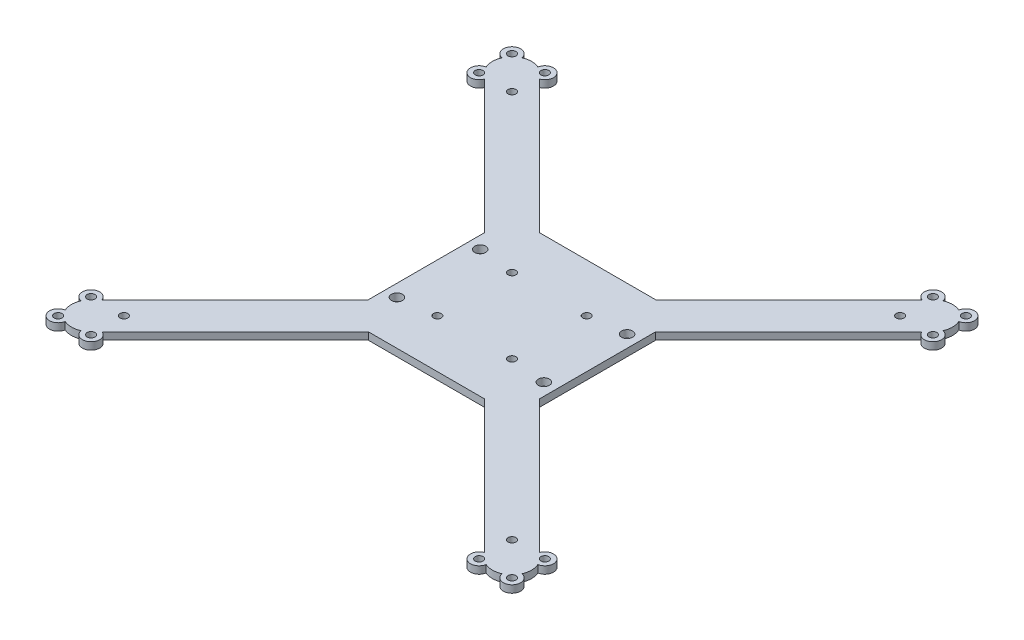
SolidWorks part; units mm, degrees
ref_plane "Front Plane" through (0, 0, 0) normal (0, 0, 1) x (1, 0, 0)
ref_plane "Top Plane" through (0, 0, 0) normal (0, 1, 0) x (1, 0, 0)
ref_plane "Right Plane" through (0, 0, 0) normal (1, 0, 0) x (0, 0, -1)
sketch "Sketch1" plane through (0, 0, 0) normal (0, 1, 0) x (1, 0, 0)
  line L1 (-23.6863, -35) -> (23.6863, -35)
  line L2 (-35, -23.6863) -> (-35, 23.6863)
  line L3 (-23.6863, 35) -> (23.6863, 35)
  line L4 (35, -23.6863) -> (35, 23.6863)
  line L5 (-35, -35) -> (42.6186, 42.6186) construction
  line L6 (-35, 35) -> (35, -35) construction
  line L7 (35, 23.6863) -> (89.3815, 78.0678)
  line L8 (23.6863, 35) -> (78.0678, 89.3815)
  line L9 (0, 0) -> (54.3815, 54.3815) construction
  line L10 (79.2432, 92.6782) -> (92.6782, 79.2432) construction
  line L11 (30, 17) -> (30, 0) construction
  line L12 (0, 0) -> (0, 23.6863) construction
  line L13 (35, -23.6863) -> (89.3815, -78.0678)
  line L14 (23.6863, -35) -> (78.0678, -89.3815)
  line L15 (-23.6863, -35) -> (-78.0678, -89.3815)
  line L16 (-35, -23.6863) -> (-89.3815, -78.0678)
  line L17 (-35, 23.6863) -> (-89.3815, 78.0678)
  line L18 (-23.6863, 35) -> (-78.0678, 89.3815)
  circle A0 centre (-15.25, 15.25) radius 1.6
  circle A1 centre (15.25, 15.25) radius 1.6
  circle A2 centre (15.25, -15.25) radius 1.6
  circle A3 centre (-15.25, -15.25) radius 1.6
  arc A5 (93.2633, 89.2274) -> (89.2274, 93.2633) centre (92.6782, 92.6782) ccw
  arc A9 (93.8536, 82.5399) -> (93.2633, 82.6939) centre (92.6782, 79.2432) ccw
  arc A10 (89.2274, 93.2633) -> (82.6939, 93.2633) centre (85.9607, 85.9607) ccw
  circle A11 centre (92.6782, 92.6782) radius 1.6
  circle A12 centre (92.6782, 79.2432) radius 1.6
  circle A13 centre (79.2432, 79.2432) radius 1.6
  circle A14 centre (79.2432, 92.6782) radius 1.6
  arc A15 (93.2633, 82.6939) -> (93.2633, 89.2274) centre (85.9607, 85.9607) ccw
  arc A16 (82.6939, 93.2633) -> (82.5399, 93.8536) centre (79.2432, 92.6782) ccw
  arc A17 (78.6581, 82.6939) -> (76.7683, 76.7683) centre (79.2432, 79.2432) ccw [skipped]
  circle A18 centre (30, 17) radius 2.25
  circle A19 centre (30, -17) radius 2.25
  circle A20 centre (-30, -17) radius 2.25
  circle A21 centre (-30, 17) radius 2.25
  arc A22 (78.0678, 89.3815) -> (82.5399, 93.8536) centre (79.2432, 92.6782) cw
  arc A23 (93.2633, -89.2274) -> (93.2633, -82.6939) centre (85.9607, -85.9607) ccw
  circle A24 centre (92.6782, 92.6782) radius 1.6
  circle A25 centre (79.2432, 79.2432) radius 1.6
  arc A26 (82.6939, -93.2633) -> (89.2274, -93.2633) centre (85.9607, -85.9607) ccw
  arc A27 (93.8536, 82.5399) -> (89.3815, 78.0678) centre (92.6782, 79.2432) cw
  arc A28 (78.0678, -89.3815) -> (82.6939, -93.2633) centre (79.2432, -92.6782) ccw
  circle A29 centre (79.2432, -92.6782) radius 1.6
  circle A30 centre (79.2432, -79.2432) radius 1.6
  circle A31 centre (92.6782, -79.2432) radius 1.6
  arc A32 (93.2633, -82.6939) -> (89.3815, -78.0678) centre (92.6782, -79.2432) ccw
  arc A33 (89.2274, -93.2633) -> (93.2633, -89.2274) centre (92.6782, -92.6782) ccw
  circle A34 centre (92.6782, -92.6782) radius 1.6
  arc A35 (-89.2274, -93.2633) -> (-82.6939, -93.2633) centre (-85.9607, -85.9607) ccw
  arc A36 (-93.2633, -82.6939) -> (-93.2633, -89.2274) centre (-85.9607, -85.9607) ccw
  arc A37 (-89.3815, -78.0678) -> (-93.2633, -82.6939) centre (-92.6782, -79.2432) ccw
  circle A38 centre (-92.6782, -79.2432) radius 1.6
  circle A39 centre (-79.2432, -79.2432) radius 1.6
  circle A40 centre (-79.2432, -92.6782) radius 1.6
  arc A41 (-82.6939, -93.2633) -> (-78.0678, -89.3815) centre (-79.2432, -92.6782) ccw
  arc A42 (-93.2633, -89.2274) -> (-89.2274, -93.2633) centre (-92.6782, -92.6782) ccw
  circle A43 centre (-92.6782, -92.6782) radius 1.6
  arc A44 (-93.2633, 89.2274) -> (-93.2633, 82.6939) centre (-85.9607, 85.9607) ccw
  arc A45 (-82.6939, 93.2633) -> (-89.2274, 93.2633) centre (-85.9607, 85.9607) ccw
  arc A46 (-78.0678, 89.3815) -> (-82.6939, 93.2633) centre (-79.2432, 92.6782) ccw
  circle A47 centre (-79.2432, 92.6782) radius 1.6
  circle A48 centre (-79.2432, 79.2432) radius 1.6
  circle A49 centre (-92.6782, 79.2432) radius 1.6
  arc A50 (-93.2633, 82.6939) -> (-89.3815, 78.0678) centre (-92.6782, 79.2432) ccw
  arc A51 (-89.2274, 93.2633) -> (-93.2633, 89.2274) centre (-92.6782, 92.6782) ccw
  circle A52 centre (-92.6782, 92.6782) radius 1.6
  point P0 (0, 0)
  point P17 (0, 0)
  point P33 (85.9607, 85.9607)
  point P42 (85.9607, 85.9607)
  point P45 (85.9607, 85.9607)
  point P47 (30, 0)
  point P51 (0, 0)
  point P53 (0, 0)
  point P54 (0, 0)
  point P118 (0, 0)
  point P119 (0, 0)
  point P120 (0, 0)
  point P121 (0, 0)
  point P122 (0, 0)
  point P123 (0, 0)
  point P124 (0, 0)
  point P125 (-83.9443, 106.2788)
  point P126 (89.2274, 77.6432)
  point P127 (82.5399, 93.8536)
  dimension "D3" = 3.2
  dimension "D9" = 4
  dimension "D11" = 7
  dimension "D13" = 3.2
  dimension "D16" = 4.5
  dimension "D1" = 70
  dimension "D2" = 70
  dimension "D4" = 30.5
  dimension "D6" = 16
  dimension "D8" = 100
  dimension "D10" = 9.5
  dimension "D15" = 17
  dimension "D12" = 30
  dimension "D5" = 4
  dimension "D14" = 4
  dimension "D17" = 2
  dimension "D18" = 4
extrude "Boss-Extrude1" add sketch "Sketch1" along normal blind 3 contours A45 A51 A44 A50 L17 L2 L16 A37 A36 A42 A35 A41 L15 L1 L14 A28 A26 A33 A23 A32 L13 L4 L7 A27 A9 A15 A5 A10 A16 A22 L8 L3 L18 A46 A52 A21 A0 A1 A2 A3 A11 A12 region at (0, 0, 0)
